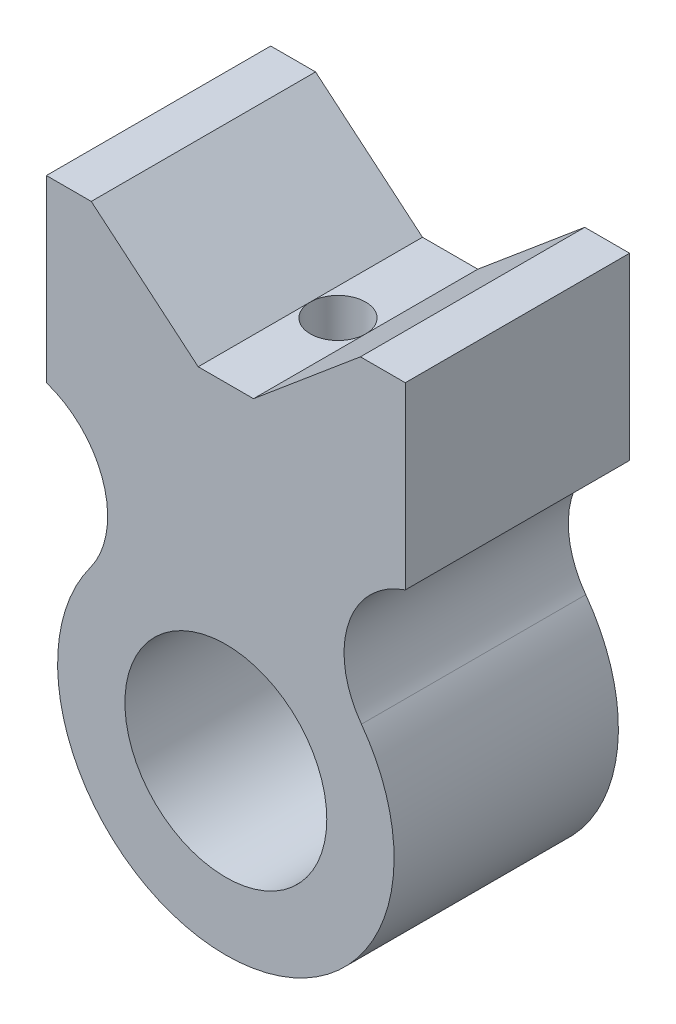
SolidWorks part; units mm, degrees
ref_plane "Alzado" through (0, 0, 0) normal (0, 0, 1) x (1, 0, 0)
ref_plane "Planta" through (0, 0, 0) normal (0, 1, 0) x (1, 0, 0)
ref_plane "Vista lateral" through (0, 0, 0) normal (1, 0, 0) x (0, 0, -1)
sketch "Croquis2" plane through (0, 0, 0) normal (0, 0, 1) x (1, 0, 0)
  line L0 (-40, 53) -> (-40, 93)
  line L1 (-40, 93) -> (-30, 93)
  line L2 (-30, 93) -> (-6.1649, 73)
  line L3 (0, 0) -> (0, 84.4561) construction
  line L4 (30, 93) -> (6.1649, 73)
  line L5 (40, 93) -> (30, 93)
  line L6 (40, 53) -> (40, 93)
  line L7 (-6.1649, 73) -> (6.1649, 73)
  circle A0 centre (0, 0) radius 22.5
  arc A1 (-30.2258, 22.1958) -> (30.2258, 22.1958) centre (0, 0) ccw
  arc A2 (-30.2258, 22.1958) -> (-40, 53) centre (-46.3462, 34.0336) ccw
  arc A3 (30.2258, 22.1958) -> (40, 53) centre (46.3462, 34.0336) cw
  dimension "D1" = 45
  dimension "D2" = 75
  dimension "D3" = 20
  dimension "D4" = 40
  dimension "D5" = 70
  dimension "D6" = 10
  dimension "D7" = 20
  dimension "D8" = 100
  dimension "D9" = 53
extrude "Saliente-Extruir1" add sketch "Croquis2" along normal blind 25 and the other way blind 25
sketch "Croquis3" plane through (0, 73, 0) normal (0, 1, 0) x (1, 0, 0)
  circle A0 centre (0, 0) radius 6.1649
extrude "Cortar-Extruir1" cut sketch "Croquis3" against normal up to next
